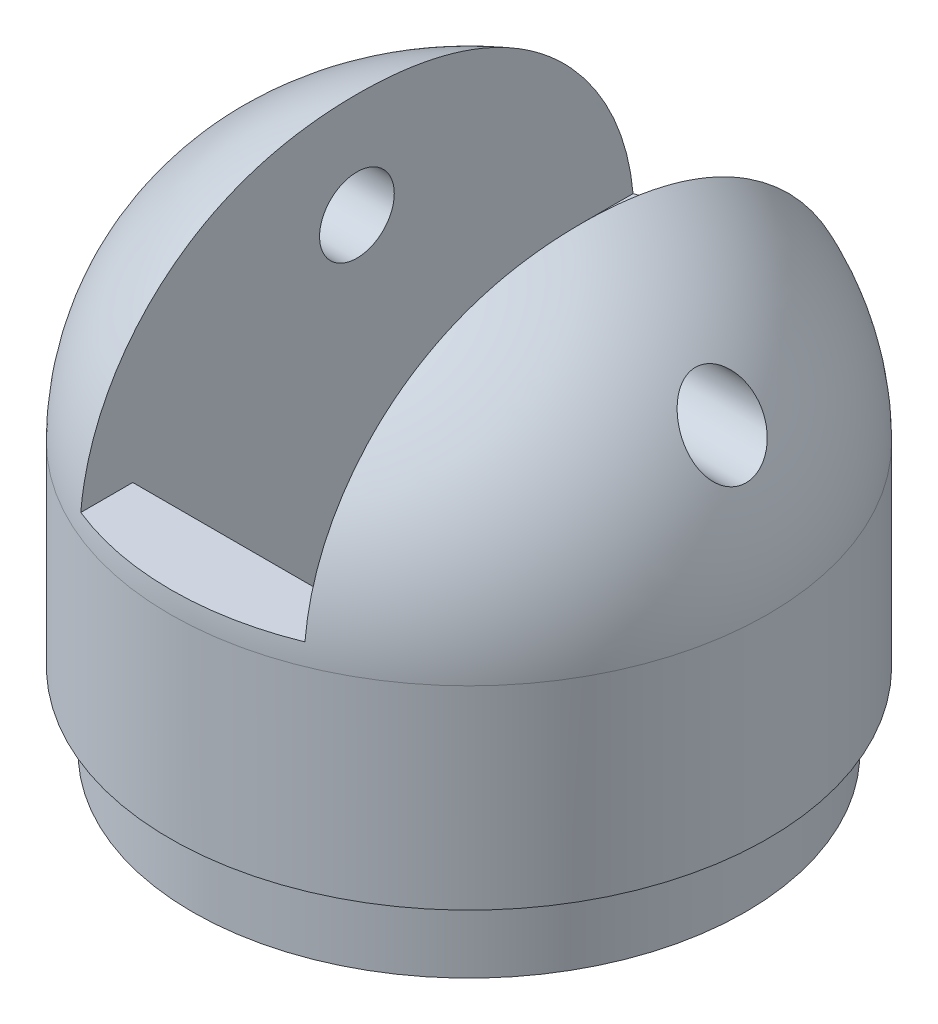
SolidWorks part; units mm, degrees
ref_plane "Front Plane" through (0, 0, 0) normal (0, 0, 1) x (1, 0, 0)
ref_plane "Top Plane" through (0, 0, 0) normal (0, 1, 0) x (1, 0, 0)
ref_plane "Right Plane" through (0, 0, 0) normal (1, 0, 0) x (0, 0, -1)
sketch "Sketch2" plane through (0, 0, 0) normal (0, 1, 0) x (1, 0, 0)
  line L0 (-7.5, 0) -> (7.5, 0)
  line L2 (-7.5, 15) -> (7.5, 15)
  line L3 (-7.5, 15) -> (-7.5, -15)
  line L4 (-7.5, -15) -> (7.5, -15)
  line L5 (7.5, 15) -> (7.5, -15)
  line L6 (-7.5, 15) -> (7.5, -15) construction
  line L7 (-7.5, -15) -> (7.5, 15) construction
  circle A0 centre (0, 0) radius 20
  point P6 (0, 0)
  dimension "D1" = 15
  dimension "D2" = 40
  dimension "D3" = 30
  dimension "D4" = 15
extrude "Boss-Extrude1" add sketch "Sketch2" along normal blind 30 contours A0 L2 L5 L4 L3 region at (-19.4343, 0, 0)
fillet "Fillet1" radius 17 1 edges at (0, 30, 20)
sketch "Sketch3" plane through (0, 0, 0) normal (0, 0, 1) x (1, 0, 0)
  line L0 (-7.5, 22.9686) -> (-7.5, 29.3936) construction
  line L1 (-7.5, 29.3936) -> (7.5, 29.3936)
  line L2 (-7.5, 29.3936) -> (-7.5, 14.3936)
  line L3 (-7.5, 14.3936) -> (7.5, 14.3936)
  line L4 (7.5, 29.3936) -> (7.5, 14.3936)
  dimension "D1" = 15
  dimension "D2" = 15
extrude "Cut-Extrude1" cut sketch "Sketch3" against normal blind 30 and the other way blind 30
sketch "Sketch4" plane through (0, 0, 0) normal (0, -1, 0) x (1, 0, 0)
  circle A0 centre (0, 0) radius 20
extrude "Boss-Extrude3" add sketch "Sketch4" along normal blind 5
sketch "Sketch5" plane through (0, -5, 0) normal (0, -1, 0) x (1, 0, 0)
  circle A0 centre (0, 0) radius 18.5
  circle A1 centre (0, 0) radius 20
  dimension "D1" = 37
  dimension "D2" = 40
extrude "Cut-Extrude2" cut sketch "Sketch5" against normal blind 5
sketch "Sketch6" plane through (0, 0, 0) normal (1, 0, 0) x (0, 0, -1)
  line L0 (-18.4788, 14.3936) -> (18.4788, 14.3936)
  line L1 (0, 14.3936) -> (0, 22.3936)
  circle A0 centre (0, 22.3936) radius 2.5
extrude "Cut-Extrude3" cut sketch "Sketch6" against normal blind 40 and the other way blind 20 contours A0 region at (0, 20.6758, -1.7178)
